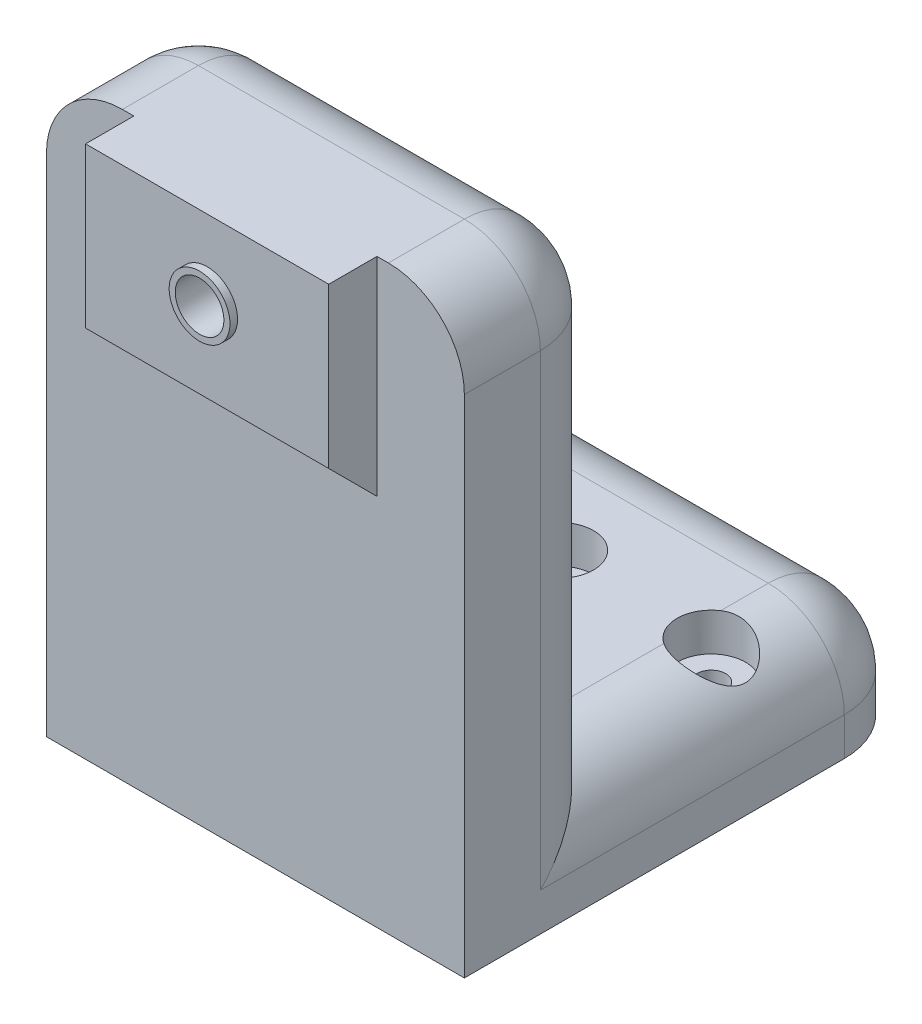
SolidWorks part; units mm, degrees
ref_plane "Front Plane" through (0, 0, 0) normal (0, 0, 1) x (1, 0, 0)
ref_plane "Top Plane" through (0, 0, 0) normal (0, 1, 0) x (1, 0, 0)
ref_plane "Right Plane" through (0, 0, 0) normal (1, 0, 0) x (0, 0, -1)
sketch "Sketch1" plane through (0, 0, 0) normal (0, 1, 0) x (1, 0, 0)
  line L1 (0, 0) -> (55, 0)
  line L2 (0, 0) -> (0, 60)
  line L3 (0, 60) -> (55, 60)
  line L4 (55, 0) -> (55, 60)
  dimension "D1" = 60
  dimension "D2" = 55
extrude "Boss-Extrude1" add sketch "Sketch1" along normal blind 15
sketch "Sketch2" plane through (0, 15, 0) normal (0, 1, 0) x (1, 0, 0)
  line L0 (55, 0) -> (55, 60) construction
  line L1 (0, 0) -> (55, 0)
  line L2 (0, 0) -> (0, 20)
  line L3 (0, 20) -> (55, 20)
  line L4 (55, 0) -> (55, 20)
  dimension "D1" = 20
extrude "Boss-Extrude2" add sketch "Sketch2" along normal blind 61.5
sketch "Sketch3" plane through (0, 0, 0) normal (0, 0, 1) x (1, 0, 0)
  line L0 (27.5, 76.5) -> (27.5, 0) construction
  line L1 (0, 76.5) -> (55, 76.5) construction
  line L2 (0, 0) -> (55, 0) construction
  circle A0 centre (27.5, 66.5) radius 3.2
  dimension "D1" = 66.5
  dimension "D2" = 6.4
extrude "Cut-Extrude1" cut sketch "Sketch3" against normal blind 10
sketch "Sketch5" plane through (0, 15, 0) normal (0, 1, 0) x (1, 0, 0)
  line L0 (0, 40) -> (55, 40) construction
  line L1 (0, 60) -> (0, 20) construction
  line L2 (55, 20) -> (55, 60) construction
  circle A0 centre (7.5, 40) radius 1.9
  circle A1 centre (27.5, 40) radius 1.9
  circle A2 centre (47.5, 40) radius 1.9
  dimension "D1" = 3
  dimension "D3" = 3.8
  dimension "55/2" = 27.5
  dimension "D4" = 20
extrude "Cut-Extrude2" cut sketch "Sketch5" against normal through all
sketch "Sketch6" plane through (0, 15, 0) normal (0, 1, 0) x (1, 0, 0)
  circle A0 centre (7.5, 40) radius 4.5
  circle A1 centre (27.5, 40) radius 4.5
  circle A2 centre (47.5, 40) radius 4.5
  dimension "D1" = 9
extrude "Cut-Extrude3" cut sketch "Sketch6" against normal blind 5
fillet "Fillet1" radius 10 10 edges at (0, 7.5, -60) (55, 7.5, -60) (27.5, 15, -60) (55, 45.75, -20) (55, 15, -40) (0, 15, -40) (0, 45.75, -20) (0, 76.5, -10) (55, 76.5, -10) (27.5, 76.5, -20)
sketch "Sketch7" plane through (0, 0, 0) normal (0, 0, 1) x (1, 0, 0)
  line L1 (11.5, 76.5) -> (43.5, 76.5)
  line L2 (11.5, 76.5) -> (11.5, 56.5)
  line L3 (11.5, 56.5) -> (43.5, 56.5)
  line L4 (43.5, 76.5) -> (43.5, 56.5)
  line L5 (11.5, 76.5) -> (43.5, 56.5) construction
  line L6 (11.5, 56.5) -> (43.5, 76.5) construction
  circle A1 centre (27.5, 66.5) radius 3.2
  point P0 (27.5, 66.5)
  dimension "D1" = 32
  dimension "D3" = 6.4
  dimension "D2" = 20
extrude "Boss-Extrude3" add sketch "Sketch7" along normal blind 6.35
chamfer "Chamfer1" distance 7.35 angle 45 1 edges at (27.5, 56.5, 0)
sketch "Sketch8" plane through (0, 0, 6.35) normal (0, 0, 1) x (1, 0, 0)
  circle A0 centre (27.5, 66.5) radius 3.2
  circle A1 centre (27.5, 66.5) radius 4
  dimension "D1" = 8
  dimension "D2" = 6.4
extrude "Boss-Extrude4" add sketch "Sketch8" along normal blind 1
